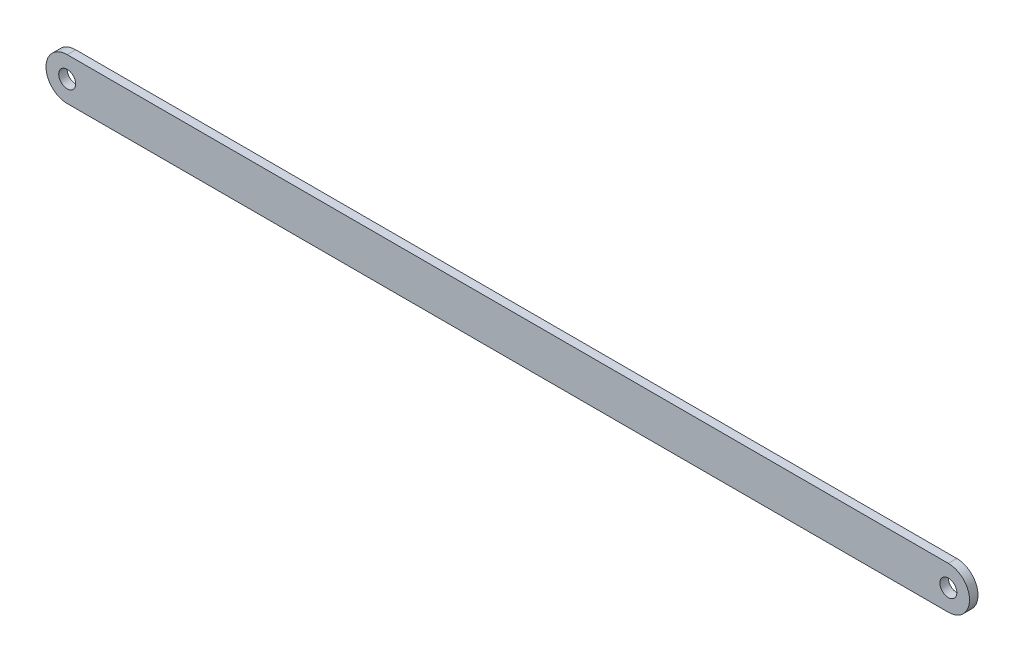
SolidWorks part; units mm, degrees
ref_plane "Front Plane" through (0, 0, 0) normal (0, 0, 1) x (1, 0, 0)
ref_plane "Top Plane" through (0, 0, 0) normal (0, 1, 0) x (1, 0, 0)
ref_plane "Right Plane" through (0, 0, 0) normal (1, 0, 0) x (0, 0, -1)
sketch "Sketch1" plane through (0, 0, 0) normal (0, 0, 1) x (1, 0, 0)
  line L0 (-260, 0) -> (260, 0) construction
  line L1 (-260, 12.5) -> (260, 12.5)
  line L2 (-260, -12.5) -> (260, -12.5)
  arc A0 (-260, 12.5) -> (-260, -12.5) centre (-260, 0) ccw
  arc A1 (260, -12.5) -> (260, 12.5) centre (260, 0) ccw
  point P2 (0, 0)
  dimension "D1" = 520
  dimension "D2" = 25
extrude "Boss-Extrude1" add sketch "Sketch1" along normal blind 5 contours A0 L2 A1 L1
hole_wizard "M8 Clearance Hole1" positions "Sketch2" profile "Sketch3" hole size "M8" standard "ANSI Metric" end condition through all
sketch "Sketch2" plane through (0, 0, 5) normal (0, 0, 1) x (1, 0, 0)
  point P3 (260, 0)
  point P6 (-260, 0)
sketch "Sketch3" plane through (260, 0, 5) normal (1, 0, 0) x (0, -1, 0)
  line L0 (0, 0) -> (0, 5)
  line L1 (0, 5) -> (5, 5)
  line L2 (5, 5) -> (5, 0)
  line L5 (5, 0) -> (0, 0)
  line L11 (0, -6.35) -> (0, 107.95) construction
  dimension "Thru Hole Dia." = 10
  dimension "Thru Hole Depth" = 5
